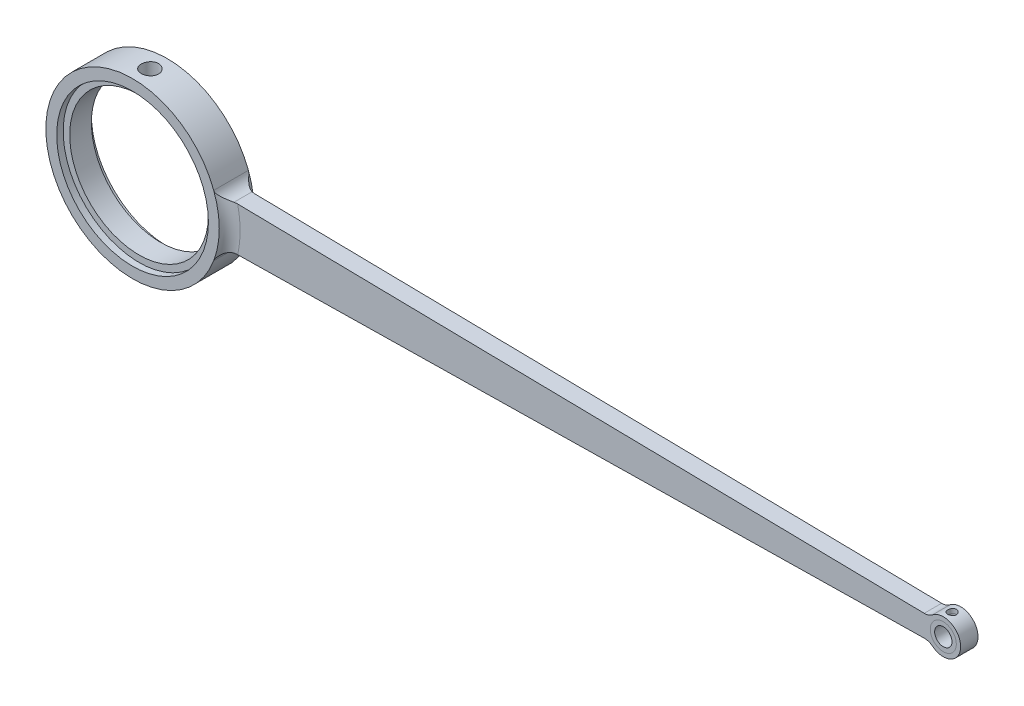
SolidWorks part; units mm, degrees
ref_plane "Front Plane" through (0, 0, 0) normal (0, 0, 1) x (1, 0, 0)
ref_plane "Top Plane" through (0, 0, 0) normal (0, 1, 0) x (1, 0, 0)
ref_plane "Right Plane" through (0, 0, 0) normal (1, 0, 0) x (0, 0, -1)
sketch "Sketch1" plane through (0, 0, 0) normal (0, 0, 1) x (1, 0, 0)
  circle A0 centre (0, 0) radius 20
  circle A1 centre (0, 0) radius 17.5
  dimension "D1" = 40
  dimension "D2" = 35
extrude "Boss-Extrude1" add sketch "Sketch1" along normal mid plane 8
sketch "Sketch2" plane through (0, 0, 0) normal (0, 0, 1) x (1, 0, 0)
  circle A0 centre (185, 0) radius 4
  circle A1 centre (185, 0) radius 3
  point P3 (0, 0)
  dimension "D1" = 8
  dimension "D2" = 6
  dimension "D3" = 185
extrude "Boss-Extrude2" add sketch "Sketch2" along normal mid plane 4 separate body
sketch "Sketch3" plane through (0, 0, 0) normal (0, 0, 1) x (1, 0, 0)
  line L0 (20, 0) -> (181, 0) construction
  line L1 (19.3348, 5.1152) -> (181.8471, 2.4615)
  line L2 (19.3348, -5.1152) -> (181.8471, -2.4615)
  line L3 (26.3903, 5) -> (26.3903, -5) construction
  line L4 (179.4918, 2.5) -> (179.4918, -2.5) construction
  circle A0 centre (0, 0) radius 20 construction
  circle A1 centre (185, 0) radius 4 construction
  arc A2 (19.3348, -5.1152) -> (19.3348, 5.1152) centre (0, 0) ccw
  arc A3 (181.8471, 2.4615) -> (181.8471, -2.4615) centre (185, 0) ccw
  dimension "D1" = 10
  dimension "D2" = 5
extrude "Boss-Extrude3" add sketch "Sketch3" along normal mid plane 4
fillet "Fillet2" radius 3 6 edges at (181.8471, -2.4615, 0) (181.8471, 2.4615, 0) (19.3348, 5.1152, 0) (20, 0, -2) (19.3348, -5.1152, 0) (20, 0, 2)
sketch "Sketch4" plane through (0, 0, 0) normal (0, 0, 1) x (1, 0, 0)
  circle A0 centre (0, 0) radius 16
  circle A1 centre (0, 0) radius 17.5 construction
  circle A2 centre (0, 0) radius 17.5
  dimension "D1" = 32
extrude "Boss-Extrude4" add sketch "Sketch4" along normal mid plane 5
sketch "Sketch5" plane through (0, 0, 2) normal (0, 0, 1) x (1, 0, 0)
  circle A0 centre (185, 0) radius 3 construction
  circle A1 centre (185, 0) radius 3
  circle A2 centre (185, 0) radius 2
  dimension "D1" = 4
extrude "Boss-Extrude5" add sketch "Sketch5" against normal up to surface (4 mm away) separate body up to face at (129.6513, 0, -2)
sketch "Sketch6" plane through (0, 0, 0) normal (0, 1, 0) x (1, 0, 0)
  line L0 (189, -2) -> (189, 2) construction
  line L1 (180.5976, -2) -> (180.5976, 2) construction
  circle A0 centre (0, 0) radius 2
  circle A1 centre (185, 0) radius 1
  point P9 (180.5976, 0)
  dimension "D1" = 4
  dimension "D2" = 2
  dimension "D3" = 4
extrude "Cut-Extrude1" cut sketch "Sketch6" along normal through all
